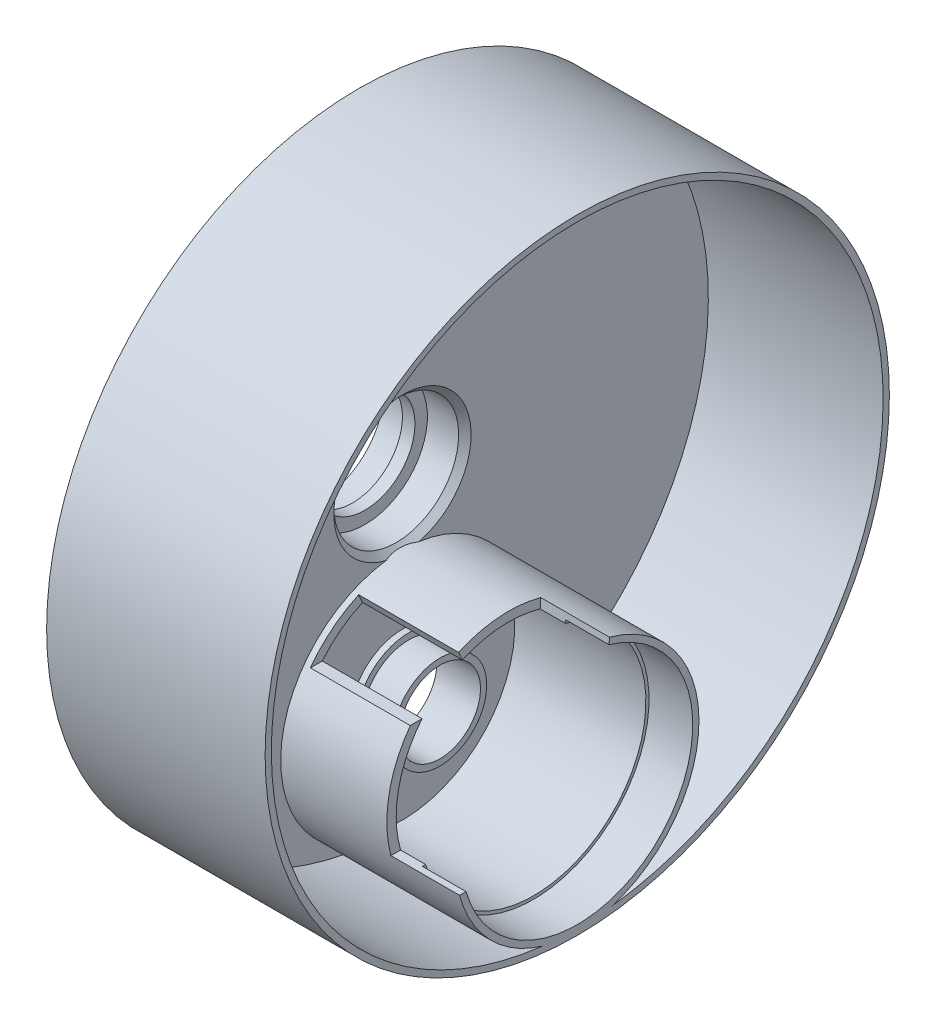
SolidWorks part; units mm, degrees
material "1060 Сплав"
ref_plane "Спереди" through (0, 0, 0) normal (0, 0, 1) x (1, 0, 0)
ref_plane "Сверху" through (0, 0, 0) normal (0, 1, 0) x (1, 0, 0)
ref_plane "Справа" through (0, 0, 0) normal (1, 0, 0) x (0, 0, -1)
sketch "Эскиз1" plane through (0, 0, 0) normal (0, 0, 1) x (1, 0, 0)
  line L0 (0, 0) -> (26039.5549, 0) construction
  line L1 (-27, 7.5) -> (-27, 8.5)
  line L2 (0, 19.5) -> (-29, 19.5)
  line L3 (-29, 19.5) -> (-29, 6.5)
  line L4 (-29, 6.5) -> (-22, 6.5)
  line L5 (-22, 6.5) -> (-22, 7.5)
  line L6 (-22, 7.5) -> (-27, 7.5)
  line L7 (-28, 8.5) -> (-28, 18)
  line L8 (-28, 18) -> (-7, 18)
  line L9 (-7, 18) -> (-7, 18.5)
  line L10 (-7, 18.5) -> (0, 18.5)
  line L11 (0, 18.5) -> (0, 19.5)
  line L12 (-27, 8.5) -> (-28, 8.5)
  dimension "D1" = 18.5
  dimension "D2" = 1
  dimension "D3" = 18
  dimension "D4" = 7
  dimension "D5" = 21
  dimension "D6" = 1
  dimension "D7" = 1
  dimension "D8" = 1
  dimension "D9" = 7.5
  dimension "D10" = 1
  dimension "D11" = 13
  dimension "D12" = 0.5
  dimension "D13" = 5
revolve "Повернуть1" add sketch "Эскиз1" angle 360 about L0
sketch "Эскиз2" plane through (0, 0, 0) normal (1, 0, 0) x (0, 0, -1)
  line L0 (0, 0) -> (0, 50000) construction
  line L1 (5.1563, 18.8059) -> (5, 16.2481)
  line L2 (5, 0) -> (5, 50000) construction
  line L3 (0, 0) -> (0, -5) construction
  line L4 (0, -5) -> (-50000, -5) construction
  line L5 (-18.8481, -5) -> (-16.2481, -5)
  line L6 (-5, 0) -> (-5, 50000) construction
  arc A0 (5, 16.2481) -> (-16.2481, -5) centre (0, 0) ccw
  arc A1 (-18.8481, -5) -> (5.1563, 18.8059) centre (0, 0) cw
  circle A2 centre (0, 0) radius 19.5 construction
  dimension "D3" = 17
  dimension "D4" = 19.5
  dimension "D1" = 5
  dimension "D2" = 5
  dimension "D5" = 2.5626
  dimension "D6" = 0
extrude "Вырез-Вытянуть1" cut sketch "Эскиз2" against normal blind 11 contours A0 L5 A1 L1
sketch "Эскиз3" plane through (0, 0, 0) normal (1, 0, 0) x (0, 0, -1)
  line L3 (-40, 11.5) -> (-12.52, 11.5)
  line L4 (0, 0) -> (-20535.6471, 45588.2353) construction
  line L5 (-6.9821, 15.5) -> (-13.2408, 29.394)
  line L6 (-13.2408, 29.394) -> (-40, 11.5)
  line L7 (0, 15.5) -> (-50000, 15.5) construction
  circle A0 centre (0, 0) radius 15.5 construction
  circle A1 centre (0, 0) radius 11.5 construction
  arc A2 (-6.9821, 15.5) -> (-12.52, 11.5) centre (0, 0) ccw
  dimension "D1" = 31
  dimension "D2" = 23
  dimension "D4" = 34
  dimension "D3" = 15.2386
  dimension "D5" = 32.1908
extrude "Вырез-Вытянуть2" cut sketch "Эскиз3" against normal blind 27
sketch "Эскиз4" plane through (-29, 0, 0) normal (-1, 0, 0) x (0, 0, 1)
  circle A1 centre (0, 30) radius 50
  circle A2 centre (0, 30) radius 10
  circle A3 centre (0, 0) radius 6.5 construction
  circle A4 centre (0, 0) radius 6.5
  dimension "D2" = 100
  dimension "D3" = 20
  dimension "D5" = 13
  dimension "D1" = 30
  dimension "D4" = 30
extrude "Бобышка-Вытянуть1" add sketch "Эскиз4" against normal blind 1
sketch "Эскиз5" plane through (-29, 0, 0) normal (-1, 0, 0) x (0, 0, 1)
  circle A0 centre (0, 30) radius 50
  circle A1 centre (0, 30) radius 49
  dimension "D1" = 100
  dimension "D2" = 98
extrude "Бобышка-Вытянуть2" add sketch "Эскиз5" against normal blind 29 and the other way blind 6
sketch "Эскиз9" plane through (0, 0, 0) normal (0, 0, 1) x (1, 0, 0)
  line L0 (-50.3474, 30) -> (12.875, 30) construction
  line L1 (-41, 40) -> (-36, 40)
  line L2 (-41, 41) -> (-29, 41)
  line L3 (-36, 40) -> (-36, 38)
  line L4 (-36, 38) -> (-34, 38)
  line L5 (-34, 38) -> (-34, 40)
  line L6 (-34, 40) -> (-29, 40)
  line L7 (-29, 40) -> (-29, 41)
  line L8 (-41, 41) -> (-41, 40)
  point P5 (-41, 40.5)
  point P12 (-34, 39)
  dimension "D1" = 30
  dimension "D2" = 12
  dimension "D3" = 5
  dimension "D4" = 1
  dimension "D5" = 7
  dimension "D6" = 2
revolve "Повернуть2" add sketch "Эскиз9" angle 360 about L0
sketch "Эскиз12" plane through (-29, 0, 0) normal (-1, 0, 0) x (0, 0, 1)
  line L0 (0, 30) -> (26.4, 30) construction
  circle A0 centre (26.4, 30) radius 5
  dimension "D2" = 10
  dimension "D1" = 26.4
extrude "Вырез-Вытянуть3" cut sketch "Эскиз12" against normal up to next
hole_wizard "Сверление под метчик M2x0.41" positions "Эскиз13" profile "Эскиз14" hole size "M2x0.4" standard "Ansi Metric" end condition through all
sketch "Эскиз13" plane through (-29, 0, 0) normal (-1, 0, 0) x (0, 0, 1)
  line L0 (26.4, 30) -> (26.4, 36.5) construction
  point P0 (26.4, 36.5)
  dimension "D1" = 6.5
sketch "Эскиз14" plane through (-29, 36.5, 26.4) normal (0, 1, 0) x (0, 0, 1)
  line L0 (0, 0) -> (0, 29)
  line L1 (0, 29) -> (0.8, 29)
  line L2 (0.8, 29) -> (0.8, 0)
  line L5 (0.8, 0) -> (0, 0)
  line L11 (0, -6.35) -> (0, 107.95) construction
  dimension "Диаметр сквозного отверстия" = 1.6
  dimension "Глубина сквозного отверстия" = 29
pattern_circular "Круговой массив1" count 3 over 360 about axis through (0.001, 30, 26.4) along (-1, 0, 0) of "Сверление под метчик M2x0.41"
sketch "Эскиз15" plane through (-29, 0, 0) normal (-1, 0, 0) x (0, 0, 1)
  circle A0 centre (0, 30) radius 11
  circle A1 centre (0, 30) radius 12
  circle A2 centre (0, 30) radius 11 construction
  dimension "D1" = 1
extrude "Бобышка-Вытянуть3" add sketch "Эскиз15" along normal blind 0.5
chamfer "Фаска1" distance 1 angle 45 1 edges at (-28, 30, 10)
